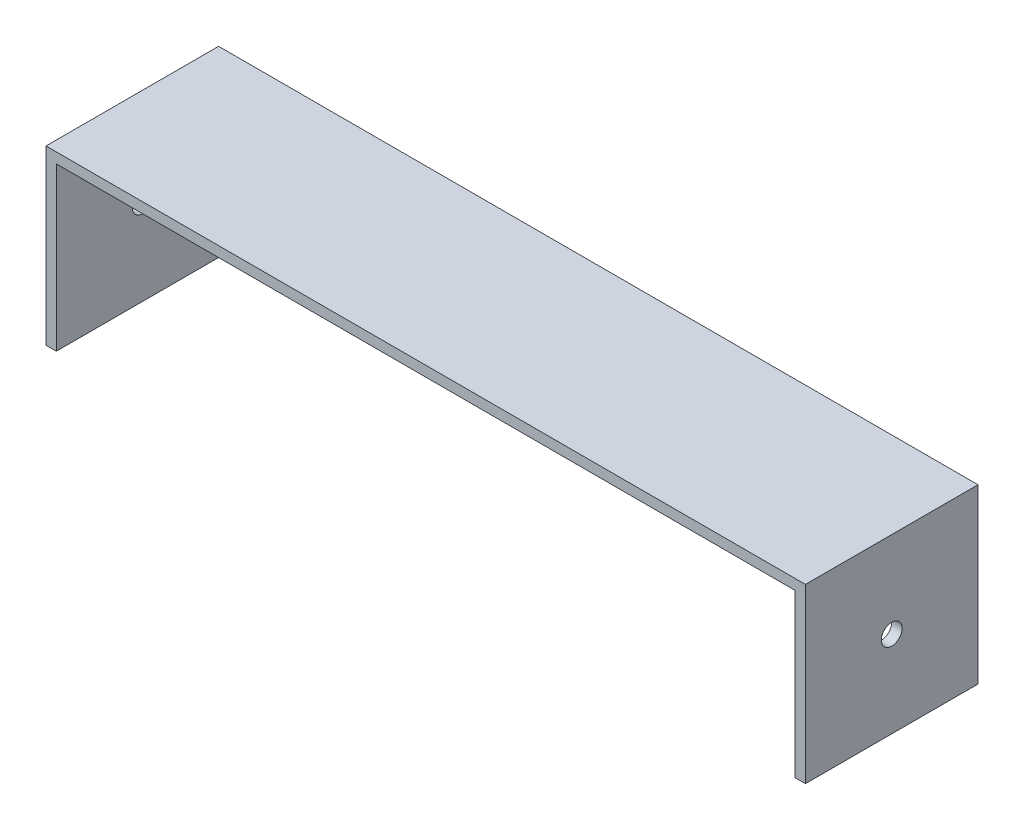
SolidWorks part; units mm, degrees
material "1060 Alloy"
ref_plane "Front Plane" through (0, 0, 0) normal (0, 0, 1) x (1, 0, 0)
ref_plane "Top Plane" through (0, 0, 0) normal (0, 1, 0) x (1, 0, 0)
ref_plane "Right Plane" through (0, 0, 0) normal (1, 0, 0) x (0, 0, -1)
sketch "Sketch3" plane through (0, 0, 0) normal (0, 1, 0) x (1, 0, 0)
  line L0 (0, 12.5) -> (0, -12.5) construction
  line L1 (-53.5, -12.5) -> (53.5, -12.5)
  line L2 (-53.5, -12.5) -> (-53.5, 12.5)
  line L3 (-53.5, 12.5) -> (53.5, 12.5)
  line L4 (53.5, -12.5) -> (53.5, 12.5)
  line L5 (-53.5, -12.5) -> (53.5, 12.5) construction
  line L6 (-53.5, 12.5) -> (53.5, -12.5) construction
  line L7 (53.5, 12.5) -> (55, 12.5)
  line L8 (53.5, 12.5) -> (53.5, -12.5)
  line L9 (53.5, -12.5) -> (55, -12.5)
  line L10 (55, 12.5) -> (55, -12.5)
  line L11 (-53.5, -12.5) -> (-55, -12.5)
  line L12 (-55, 12.5) -> (-55, -12.5)
  line L13 (-53.5, 12.5) -> (-55, 12.5)
  line L14 (-53.5, 12.5) -> (-53.5, -12.5)
  point P0 (0, 0)
  dimension "D1" = 107
  dimension "D2" = 25
  dimension "D3" = 1.5
extrude "Boss-Extrude1" add sketch "Sketch3" against normal blind 1.5 contours L1 L4 L3 L2 region at (0, 0, 0)
extrude "Boss-Extrude2" add sketch "Sketch3<3>" against normal blind 25 contours L2 L13 L12 L11 | L10 L7 L4 L9 region at (-54.25, 0, 0) region at (54.25, 0, 0)
sketch "Sketch3<3>" plane through (0, 0, 0) normal (0, 1, 0) x (1, 0, 0) same geometry as "Sketch3"
sketch "Sketch4" plane through (55, 0, 0) normal (1, 0, 0) x (0, 0, -1)
  line L0 (12.5, -25) -> (12.5, 0) construction
  circle A0 centre (0, -12.5) radius 1.5
  point P4 (12.5, -12.5)
  dimension "D1" = 3
extrude "Cut-Extrude1" cut sketch "Sketch4" against normal through all
